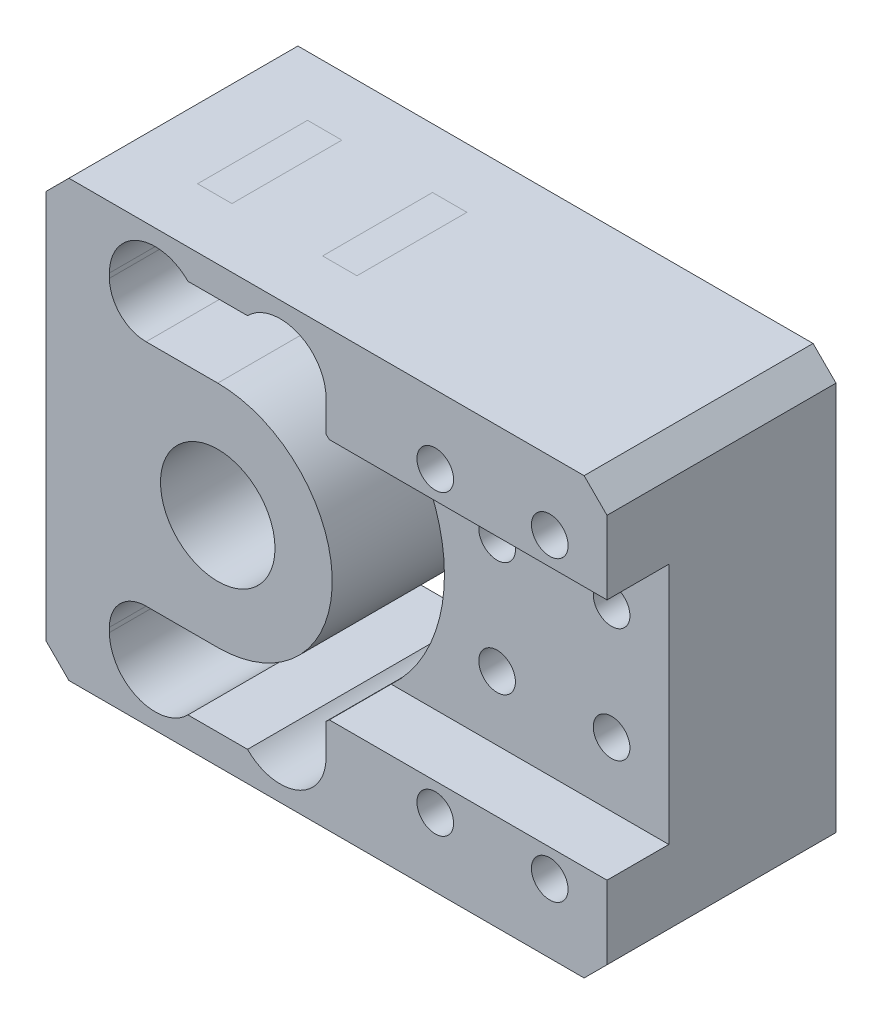
SolidWorks part; units mm, degrees
material "6061 Alloy"
ref_plane "Front Plane" through (0, 0, 0) normal (0, 0, 1) x (1, 0, 0)
ref_plane "Top Plane" through (0, 0, 0) normal (0, 1, 0) x (1, 0, 0)
ref_plane "Right Plane" through (0, 0, 0) normal (1, 0, 0) x (0, 0, -1)
sketch "Sketch1" plane through (0, 0, 0) normal (0, 0, 1) x (1, 0, 0)
  line L1 (7.5, -9.5) -> (-7.5, -9.5)
  line L2 (7.5, -9.5) -> (7.5, 9.5)
  line L3 (7.5, 9.5) -> (-7.5, 9.5)
  line L4 (-7.5, -9.5) -> (-7.5, 9.5)
  line L5 (7.5, -9.5) -> (-7.5, 9.5) construction
  line L6 (7.5, 9.5) -> (-7.5, -9.5) construction
  point P0 (0, 0)
  dimension "D1" = 19
  dimension "D2" = 15
extrude "Boss-Extrude1" add sketch "Sketch1" along normal blind 5 and the other way blind 5
sketch "Sketch2" plane through (0, 0, 0) normal (0, 0, 1) x (1, 0, 0)
  line L1 (-2.73, 8.8) -> (-2.73, 9.5) construction
  line L2 (7.5, 9.5) -> (-7.5, 9.5) construction
  line L3 (0, 0) -> (0, -5.2202) construction
  circle A0 centre (-2.73, 6.8) radius 2
  dimension "D2" = 5.46
  dimension "D1" = 2.7
  dimension "D3" = 4
extrude "Cut-Extrude1" cut sketch "Sketch2" against normal blind 6 and the other way blind 10
mirror "Mirror3" about plane through (0, 0, 0) normal (0, 1, 0) of "Cut-Extrude1"
sketch "Sketch5" plane through (0, 0, 0) normal (0, 0, 1) x (1, 0, 0)
  line L0 (0, 0) -> (0, 8.2078) construction
  circle A0 centre (2.73, 6.8) radius 2
  circle A1 centre (-2.73, 6.8) radius 2 construction
  point P2 (-2.73, 6.8)
extrude "Cut-Extrude4" cut sketch "Sketch5" against normal blind 17 and the other way blind 17
sketch "Sketch6" plane through (0, 0, 0) normal (0, 0, 1) x (1, 0, 0)
  circle A0 centre (2.73, -6.8) radius 2
  circle A3 centre (2.73, 6.8) radius 2 construction
  point P5 (-2.73, -6.8)
  point P6 (2.73, 6.8)
extrude "Cut-Extrude5" cut sketch "Sketch6" against normal blind 17 and the other way blind 17
sketch "Sketch10" plane through (0, 0, 0) normal (0, 0, 1) x (1, 0, 0)
  line L0 (-0.73, 6.8) -> (-4.73, 6.8) construction
  line L1 (4.73, -6.8) -> (-4.73, -6.8)
  line L2 (4.73, -6.8) -> (4.73, 6.8)
  line L3 (4.73, 6.8) -> (-4.73, 6.8)
  line L4 (-4.73, -6.8) -> (-4.73, 6.8)
  line L5 (4.73, -6.8) -> (-4.73, 6.8) construction
  line L6 (4.73, 6.8) -> (-4.73, -6.8) construction
  circle A0 centre (-2.73, 6.8) radius 2 construction
  point P0 (0, 0)
extrude "Cut-Extrude6" cut sketch "Sketch10" against normal through all and the other way through all
sketch "Sketch7" plane through (0, 0, 0) normal (0, 0, 1) x (1, 0, 0)
  circle A0 centre (0, 0) radius 2.5
  circle A1 centre (0, 0) radius 5
  dimension "D1" = 10
  dimension "D2" = 5
extrude "Boss-Extrude2" add sketch "Sketch7" along normal up to surface (5 mm away) and the other way up to surface (5 mm away) separate body up to face at (0, 0, 5) other way up to face at (0, 0, -5)
sketch "Sketch8" plane through (0, 0, 0) normal (0, 0, 1) x (1, 0, 0)
  line L0 (0, 5) -> (-7.5, 5)
  line L1 (-7.5, 5) -> (-7.5, 0)
  line L2 (-7.5, 0) -> (-5, 0)
  line L3 (-5, 0) -> (0, 5)
  line L4 (-7.5, 9.5) -> (-7.5, -9.5) construction
  circle A0 centre (0, 0) radius 5 construction
extrude "Boss-Extrude3" add sketch "Sketch8" along normal up to surface (5 mm away) and the other way up to surface (5 mm away) up to face at (0, 0, 5) other way up to face at (0, 0, -5)
mirror "Mirror7" about plane through (0, 0, 0) normal (0, 1, 0) of "Boss-Extrude3"
fillet "Fillet1" radius 1.6 2 edges at (-4.73, -5, 0) (-4.73, 5, 0)
sketch "Sketch11" plane through (0, 0, 5) normal (0, 0, 1) x (1, 0, 0)
  line L0 (7.5, 9.5) -> (-7.5, 9.5) construction
  line L1 (4.73, 9.5) -> (17, 9.5)
  line L2 (4.73, 9.5) -> (4.73, -9.5)
  line L3 (4.73, -9.5) -> (17, -9.5)
  line L4 (17, 9.5) -> (17, -9.5)
  line L5 (-7.5, -9.5) -> (7.5, -9.5) construction
  line L6 (4.73, -6.8) -> (4.73, -1.6208) construction
  dimension "D1" = 17
extrude "Boss-Extrude4" add sketch "Sketch11" against normal up to surface (10 mm away) up to face at (-0.365, -6.2309, -5)
chamfer "Chamfer1" distance 1 angle 45 4 edges at (-7.5, -9.5, 0) (17, -9.5, 0) (17, 9.5, 0) (-7.5, 9.5, 0)
sketch "Sketch16" plane through (0, 0, 5) normal (0, 0, 1) x (1, 0, 0)
  line L1 (-3.13, 5) -> (2.6756, 5)
  line L2 (-3.13, 5) -> (-3.13, 8.2)
  line L3 (-3.13, 8.2) -> (2.6756, 8.2)
  line L4 (2.6756, 5) -> (2.6756, 8.2)
  dimension "D1" = 3.2
extrude "Cut-Extrude8" cut sketch "Sketch16" against normal blind 11.5
mirror "Mirror8" about plane through (0, 0, 0) normal (0, 1, 0) of "Cut-Extrude8"
sketch "Sketch17" plane through (0, 0, 5) normal (0, 0, 1) x (1, 0, 0)
  line L0 (0, 0) -> (11.815, 0) construction
  arc A0 (3.2674, -5.1511) -> (3.2674, 5.1511) centre (0, 0) ccw construction
  arc A1 (0, -5) -> (4.73, -1.6208) centre (0, 0) ccw construction
  arc A2 (2.6782, -4.2223) -> (2.6782, 4.2223) centre (0, 0) ccw
  arc A3 (3.8566, -6.08) -> (3.8566, 6.08) centre (0, 0) ccw
  arc A4 (2.6782, -4.2223) -> (3.8566, -6.08) centre (3.2674, -5.1511) ccw
  arc A5 (2.6782, 4.2223) -> (3.8566, 6.08) centre (3.2674, 5.1511) cw
  arc A6 (4.73, 1.6208) -> (0, 5) centre (0, 0) ccw construction
  dimension "D1" = 1.1
  dimension "D3" = 1.1
extrude "Cut-Extrude9" cut sketch "Sketch17" against normal blind 11.5
sketch "Sketch18" plane through (0, 0, 0) normal (0, 1, 0) x (1, 0, 0)
  line L0 (-2.73, -5) -> (-2.73, 5) construction
  line L1 (-1.98, -2.4) -> (-3.48, -2.4)
  line L2 (-1.98, -2.4) -> (-1.98, 2.4)
  line L3 (-1.98, 2.4) -> (-3.48, 2.4)
  line L4 (-3.48, -2.4) -> (-3.48, 2.4)
  line L5 (-1.98, -2.4) -> (-3.48, 2.4) construction
  line L6 (-1.98, 2.4) -> (-3.48, -2.4) construction
  point P0 (-2.73, 0)
  dimension "D1" = 4.8
  dimension "D2" = 1.5
split line "Split Line1"
split line "Split Line2"
sketch "Sketch18<2>" plane through (0, 0, 0) normal (0, 1, 0) x (1, 0, 0) same geometry as "Sketch18"
sketch "Sketch19" plane through (0, 0, 0) normal (0, 1, 0) x (1, 0, 0)
  line L0 (2.73, -5) -> (2.73, 5) construction
  line L1 (3.48, -2.4) -> (1.98, -2.4)
  line L2 (3.48, -2.4) -> (3.48, 2.4)
  line L3 (3.48, 2.4) -> (1.98, 2.4)
  line L4 (1.98, -2.4) -> (1.98, 2.4)
  line L5 (3.48, -2.4) -> (1.98, 2.4) construction
  line L6 (3.48, 2.4) -> (1.98, -2.4) construction
  line L7 (-3.48, 2.4) -> (-1.98, 2.4) construction
  line L8 (-3.48, -2.4) -> (-3.48, 2.4) construction
  point P0 (2.73, 0)
split line "Split Line4"
split line "Split Line5"
sketch "Sketch19<3>" plane through (0, 0, 0) normal (0, 1, 0) x (1, 0, 0) same geometry as "Sketch19"
sketch "Sketch20" plane through (0, 0, 5) normal (0, 0, 1) x (1, 0, 0)
  line L0 (17, -8.5) -> (17, 8.5) construction
  line L1 (17, 5.3) -> (4.73, 5.3)
  line L2 (17, 5.3) -> (17, -5.3)
  line L3 (17, -5.3) -> (4.73, -5.3)
  line L4 (4.73, 5.3) -> (4.73, -5.3) construction
  line L5 (0, 0) -> (17.9159, 0) construction
  line L6 (4.73, 5.4284) -> (4.73, 6.8) construction
  arc A0 (4.73, 5.3) -> (4.73, -5.3) centre (0, 0) cw
  dimension "D1" = 10.6
extrude "Cut-Extrude10" cut sketch "Sketch20" against normal blind 2.7
hole_wizard "Trou taraudé M21" positions "Sketch23" profile "Sketch22" tap size "M2" standard "Iso" end condition through all
sketch "Sketch23" plane through (0, 0, 5) normal (0, 0, 1) x (1, 0, 0)
  line L0 (0, 0) -> (16.8835, 0) construction
  line L4 (9.5, -2.5) -> (14.5, -2.5)
  line L5 (9.5, -2.5) -> (9.5, 2.5)
  line L6 (9.5, 2.5) -> (14.5, 2.5)
  line L7 (14.5, -2.5) -> (14.5, 2.5)
  line L8 (9.5, -2.5) -> (14.5, 2.5) construction
  line L9 (9.5, 2.5) -> (14.5, -2.5) construction
  line L10 (12, -2.5) -> (12, 0) construction
  point P0 (14.5, 2.5)
  point P1 (14.5, -2.5)
  point P13 (9.5, 2.5)
  point P15 (9.5, -2.5)
  point P154 (9.5, 6.5)
  point P156 (14.5, 6.5)
  point P158 (9.5, -6.5)
  point P160 (14.5, -6.5)
  dimension "D1" = 5
  dimension "D2" = 12
  dimension "D3" = 5
  dimension "D4" = 13
sketch "Sketch22" plane through (14.5, 2.5, 5) normal (1, 0, 0) x (0, -1, 0)
  line L0 (0, 0) -> (0, 10)
  line L1 (0, 10) -> (0.8, 10)
  line L2 (0.8, 10) -> (0.8, 0)
  line L5 (0.8, 0) -> (0, 0)
  line L11 (0, -6.35) -> (0, 107.95) construction
  dimension "Diamètre du trou pour taraudage jusqu'au prochain" = 1.6
  dimension "Profondeur du trou pour taraudage jusqu'au prochain" = 10
cosmetic thread "Filetage de perçage1" parameters "D2"=2
cosmetic thread "Filetage de perçage2" parameters "D2"=2
cosmetic thread "Filetage de perçage3" parameters "D2"=2
cosmetic thread "Filetage de perçage4" parameters "D2"=2
cosmetic thread "Filetage de perçage5" parameters "D2"=2
cosmetic thread "Filetage de perçage6" parameters "D2"=2
cosmetic thread "Filetage de perçage7" parameters "D2"=2
cosmetic thread "Filetage de perçage8" parameters "D2"=2
hole_wizard "Trou taraudé M2.51" positions "Sketch25" profile "Sketch26" tap size "M2.5" standard "Iso"
sketch "Sketch25" plane through (-7.5, 0, 0) normal (-1, 0, 0) x (0, 0, 1)
  point P0 (0, 0)
sketch "Sketch26" plane through (-7.5, 0, 0) normal (0, 1, 0) x (0, 0, 1)
  line L0 (0, 0) -> (0, 8.8659)
  line L1 (0, 8.8659) -> (1.025, 8.25)
  line L2 (1.025, 8.25) -> (1.025, 0)
  line L5 (1.025, 0) -> (0, 0)
  line L10 (0, 8.8659) -> (-1.025, 8.25) construction
  line L11 (0, -6.35) -> (0, 107.95) construction
  dimension "Diamètre du trou pour taraudage" = 2.05
  dimension "Profondeur du trou pour taraudage" = 8.25
  dimension "Angle de pointe" = 118
cosmetic thread "Filetage de perçage9" parameters "D1"=5.2198, "D2"=2.5
sketch "Sketch27" [suppressed] plane through (0, 0, 5) normal (0, 0, 1) x (1, 0, 0)
  line L0 (16, 9.5) -> (-6.5, 9.5) construction
  line L1 (4.6035, 7.5) -> (7.2, 7.5)
  line L2 (4.6035, 7.5) -> (4.6035, 3.45)
  line L3 (4.6035, 3.45) -> (7.2, 3.45)
  line L4 (7.2, 7.5) -> (7.2, 3.45)
  arc A0 (4.73, 6.8) -> (1.3017, 8.2) centre (2.73, 6.8) ccw construction
  arc A1 (4.8734, -5.3) -> (4.8734, 5.3) centre (0, 0) ccw construction
  dimension "D1" = 2
extrude "Cut-Extrude12" [suppressed] cut sketch "Sketch27" against normal blind 10
mirror "Mirror9" [suppressed] about plane through (0, 0, 0) normal (0, 1, 0)
sketch "Sketch28" [suppressed] plane through (0, 0, 2.3) normal (0, 0, 1) x (1, 0, 0)
  line L1 (7.2, 3.45) -> (6.3196, 3.45)
  line L2 (7.2, 3.45) -> (7.2, -3.45)
  line L3 (7.2, -3.45) -> (6.3196, -3.45)
  line L4 (6.3196, 3.45) -> (6.3196, -3.45)
extrude "Cut-Extrude13" [suppressed] cut sketch "Sketch28" against normal blind 10
fillet "Fillet2" [suppressed] radius 2
